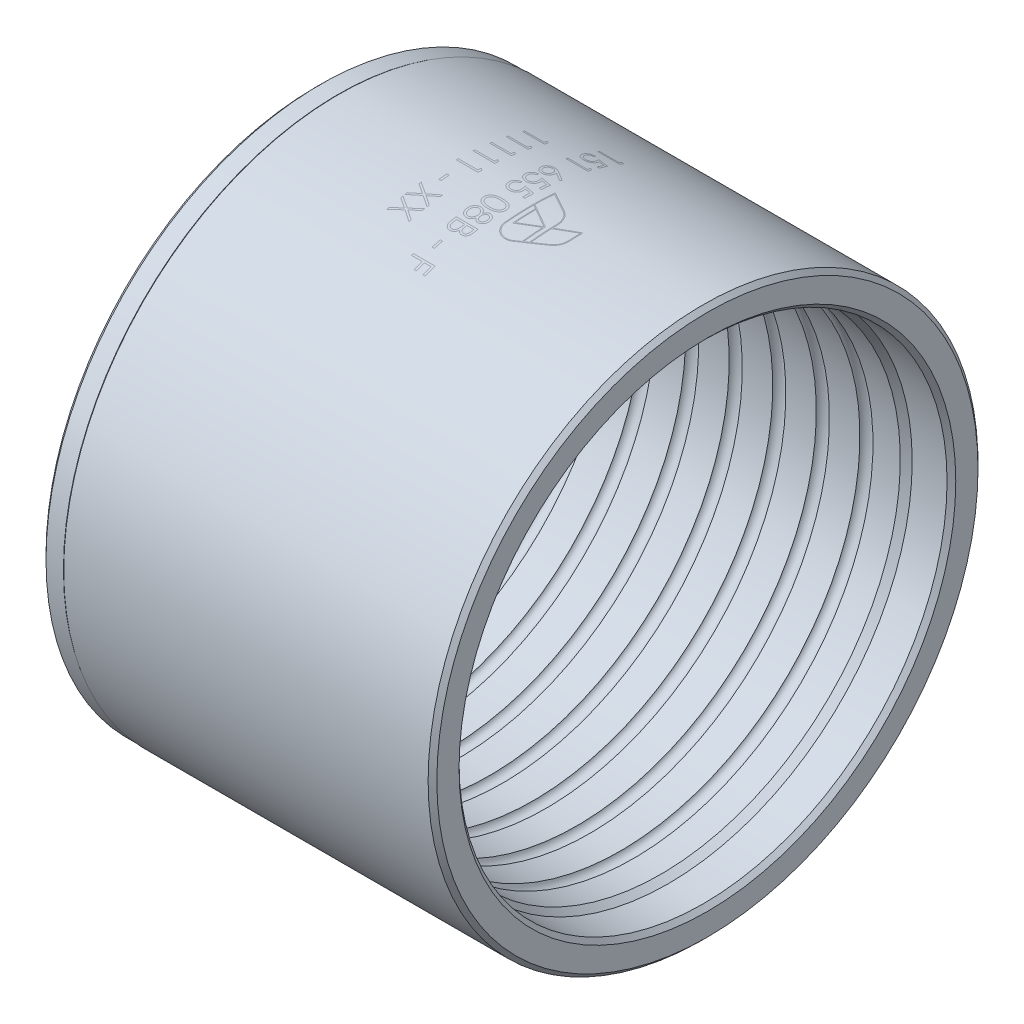
SolidWorks part; units mm, degrees
material "PB01 (C90710) Bronze"
ref_plane "Front Plane" through (0, 0, 0) normal (0, 0, 1) x (1, 0, 0)
ref_plane "Top Plane" through (0, 0, 0) normal (0, 1, 0) x (1, 0, 0)
ref_plane "Right Plane" through (0, 0, 0) normal (1, 0, 0) x (0, 0, -1)
sketch "Sketch1" plane through (0, 0, 0) normal (0, 0, 1) x (1, 0, 0)
  line L0 (0, 27.5) -> (0, 31.5)
  line L1 (0, 31.5) -> (2.5, 31.5)
  line L2 (2.5, 31.5) -> (2.5866, 31.55)
  line L3 (2.5866, 31.55) -> (44.9, 31.55)
  line L4 (44.9, 31.55) -> (44.9, 28)
  line L5 (44.9, 28) -> (40.4, 28)
  line L6 (40.4, 28) -> (39.534, 27.5)
  line L7 (39.534, 27.5) -> (36.4, 27.5)
  line L8 (4.9, 27.5) -> (0, 27.5)
  line L9 (9.9, 27.5) -> (6.4, 27.5)
  line L10 (14.9, 27.5) -> (11.4, 27.5)
  line L11 (19.9, 27.5) -> (16.4, 27.5)
  line L12 (24.9, 27.5) -> (21.4, 27.5)
  line L13 (29.9, 27.5) -> (26.4, 27.5)
  line L14 (34.9, 27.5) -> (31.4, 27.5)
  line L15 (0, 0) -> (103.2975, 0) construction
  arc A0 (6.4, 27.5) -> (4.9, 27.5) centre (5.65, 27.1875) ccw
  arc A1 (11.4, 27.5) -> (9.9, 27.5) centre (10.65, 27.1875) ccw
  arc A2 (16.4, 27.5) -> (14.9, 27.5) centre (15.65, 27.1875) ccw
  arc A3 (21.4, 27.5) -> (19.9, 27.5) centre (20.65, 27.1875) ccw
  arc A4 (26.4, 27.5) -> (24.9, 27.5) centre (25.65, 27.1875) ccw
  arc A5 (31.4, 27.5) -> (29.9, 27.5) centre (30.65, 27.1875) ccw
  arc A6 (36.4, 27.5) -> (34.9, 27.5) centre (35.65, 27.1875) ccw
  dimension "D1" = 4.5
  dimension "D9" = 56
  dimension "D2" = 30
  dimension "D3" = 56
  dimension "D4" = 55
  dimension "D5" = 2.5
  dimension "D6" = 63
  dimension "D7" = 30
  dimension "D8" = 1.5
  dimension "D10" = 40
  dimension "D11" = 5
  dimension "D12" = 63.1
  dimension "D13" = 44.9
revolve "Revolve1" add sketch "Sketch1" angle 360 about L15
ref_point "Point1"
ref_plane "Plane1" through (39.534, 0, 0) normal (1, 0, 0) x (0, 0, -1)
chamfer "Chamfer2" distance 0.5 angle 45 3 edges at (44.9, 0, 31.55) (44.9, 0, 28) (0, 0, 31.5)
chamfer "Chamfer3" distance 2.5 angle 20 1 edges at (0, 0, 27.5) first distance on face at (4.9, 0, 27.5)
sketch "Sketch2" plane through (0, 0, 0) normal (0, 1, 0) x (1, 0, 0)
  line L0 (21.0943, 20.5977) -> (21.0943, -19.4607) construction
  line L1 (24.6824, 6.3736) -> (24.6824, -5.7024) construction
  text T0 "151 655 08B - F\r\n11111 - XX" font "Century Gothic" height 2.5
  line B0 (24.6824, -3.0156) -> (24.6824, 0.2528)
  line B1 (25.3487, -2.5315) -> (25.3487, -0.1261)
  line B2 (24.7824, 0.1959) -> (25.2487, -0.0692)
  line B3 (28.1266, -1.0052) -> (28.1266, -0.4352)
  line B4 (30.3905, 0.2528) -> (28.1266, -1.0052)
  line B5 (25.3487, -2.5315) -> (27.4959, -1.3471)
  line B6 (27.4959, -3.9765) -> (26.9795, -4.2753)
  line B7 (30.3905, -1.3512) -> (30.3905, 0.2528)
  line B8 (28.1266, -3.6325) -> (27.4959, -3.9765)
  line B9 (28.1266, -3.6325) -> (29.5832, -2.7687)
  line B10 (24.6824, 0.2528) -> (24.6824, 2.7502)
  line B11 (27.1516, 1.3462) -> (24.6824, 2.7502)
  line B12 (27.5962, -3.8308) -> (28.0266, -3.5756)
  line B13 (30.2905, -1.3512) -> (30.2905, 0.0828)
  line B14 (30.2905, 0.0828) -> (28.1266, -1.1196)
  line B15 (28.0266, -0.4352) -> (28.0266, -3.5756)
  line B16 (27.0998, 1.2605) -> (24.7824, 2.5783)
  line B17 (24.7824, 0.311) -> (24.7824, 2.5783)
  line B18 (27.5962, -1.2891) -> (27.5962, -3.8308)
  line B19 (24.7824, 0.311) -> (27.5962, -1.2891)
  line B20 (27.4959, -3.861) -> (26.9275, -4.1898)
  line B21 (24.7824, -3.0156) -> (24.7824, 0.1959)
  line B22 (28.1266, -1.1196) -> (28.1266, -3.5163)
  line B23 (28.1266, -3.5163) -> (29.5322, -2.6827)
  line B24 (25.2487, -2.7009) -> (25.2487, -0.0692)
  line B25 (25.2487, -2.7009) -> (27.4959, -1.4613)
  line B26 (27.4959, -1.4613) -> (27.4959, -3.861)
  line B27 (25.3487, -0.1261) -> (27.4959, -1.3471)
  arc B28 (29.5832, -2.7687) -> (30.3905, -1.3512) centre (28.7426, -1.3512) ccw
  arc B29 (24.6824, -3.0156) -> (26.9795, -4.2753) centre (26.1763, -3.0156) ccw
  arc B30 (28.1266, -0.4352) -> (27.1516, 1.3462) centre (26.0119, -0.4352) ccw
  arc B31 (29.5322, -2.6827) -> (30.2905, -1.3512) centre (28.7426, -1.3512) ccw
  arc B32 (28.0266, -0.4352) -> (27.0998, 1.2605) centre (26.0119, -0.4352) ccw
  arc B33 (24.7824, -3.0156) -> (26.9275, -4.1898) centre (26.1763, -3.0156) ccw
sketch_block_instance "SKETCH LOGO-1"
sketch_block "SKETCH LOGO" parameters "D1"=29.059, "D2"=11.4163, "D3"=29.624, "D4"=6.8884
wrap "Wrap1" sketch "Sketch2" wrap type scribe source sketch "Sketch2" face at (44.4, 0, 31.55)
